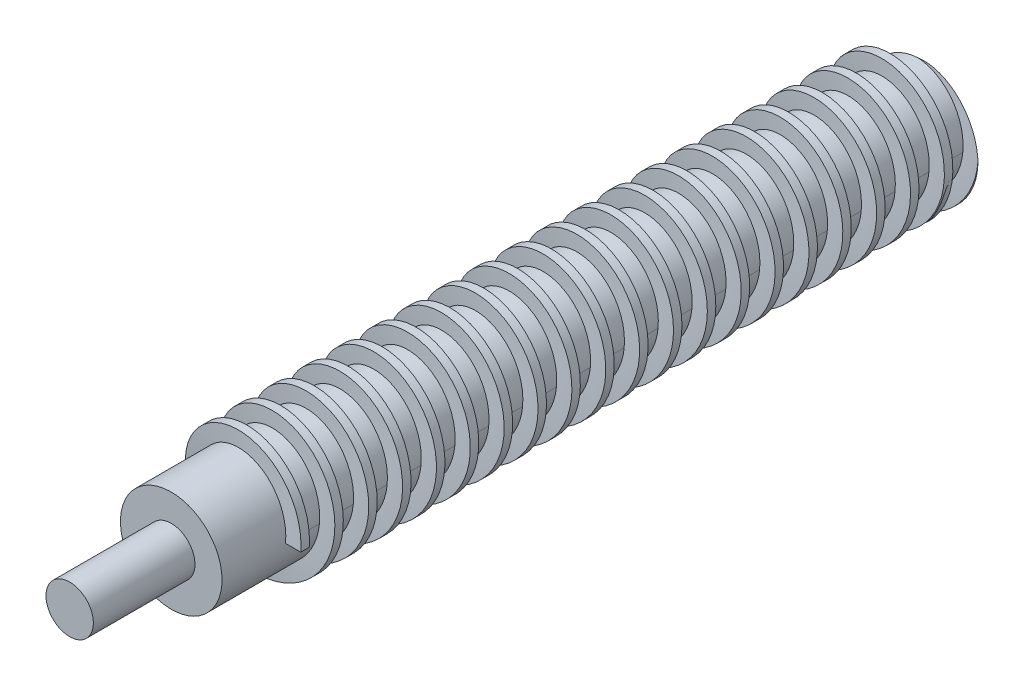
SolidWorks part; units mm, degrees
material "AISI 304"
ref_plane "Спереди" through (0, 0, 0) normal (0, 0, 1) x (1, 0, 0)
ref_plane "Сверху" through (0, 0, 0) normal (0, 1, 0) x (1, 0, 0)
ref_plane "Справа" through (0, 0, 0) normal (1, 0, 0) x (0, 0, -1)
ref_plane "Плоскость1" through (0, 0, -17) normal (0, 0, 1) x (1, 0, 0)
sketch "Эскиз1" plane through (0, 0, 0) normal (0, 0, 1) x (1, 0, 0)
  circle A0 centre (0, 0) radius 15
  dimension "D1" = 30
sketch "Эскиз2" plane through (0, 0, 0) normal (0, 1, 0) x (1, 0, 0)
  line L0 (15, 0) -> (-4.9813, 0) construction
  line L1 (15, 1.25) -> (19.5, 1.25)
  line L2 (15, 1.25) -> (15, -1.25)
  line L3 (15, -1.25) -> (19.5, -1.25)
  line L4 (19.5, 1.25) -> (19.5, -1.25)
  dimension "D1" = 2.5
  dimension "D2" = 15
  dimension "D3" = 19.5
curve "Спираль1" pitch 10 height 210 radius 15 left hand yes centre (0, 0, 0) axis (0, 0, -1) start towards (1, 0, 0)
sweep "По траектории1" add profiles "Эскиз2" path "Спираль1"
sketch "Эскиз3" plane through (0, 0, 0) normal (0, 1, 0) x (1, 0, 0)
  line L0 (0, -50) -> (7, -50)
  line L1 (7, -50) -> (7, -20)
  line L2 (7, -20) -> (15, -20)
  line L3 (15, -20) -> (15, 210)
  line L4 (15, 210) -> (0, 210)
  line L5 (0, 210) -> (0, -50)
  line L6 (0, -59.6319) -> (0, 170.3599) construction
  dimension "D1" = 260
  dimension "D2" = 50
  dimension "D3" = 30
  dimension "D4" = 14
revolve "Повернуть1" add sketch "Эскиз3" angle 360 mid plane about L6
sketch "Эскиз4" plane through (0, 0, 0) normal (0, -1, 0) x (0, 0, -1)
  line L0 (274.0415, 0) -> (145.9291, 0) construction
  line L1 (211.25, 0) -> (210, 0)
  line L2 (211.25, 0) -> (211.25, 19.5)
  line L3 (211.25, 19.5) -> (198.7417, 19.5)
  line L4 (210, 0) -> (198.7417, 19.5)
  line L5 (1.25, 19.5) -> (-1.25, 19.5) construction
  line L6 (210, -15) -> (210, 15) construction
  dimension "D1" = 60
revolve "Вырез-Повернуть1" cut sketch "Эскиз4" angle 360 mid plane about L0
